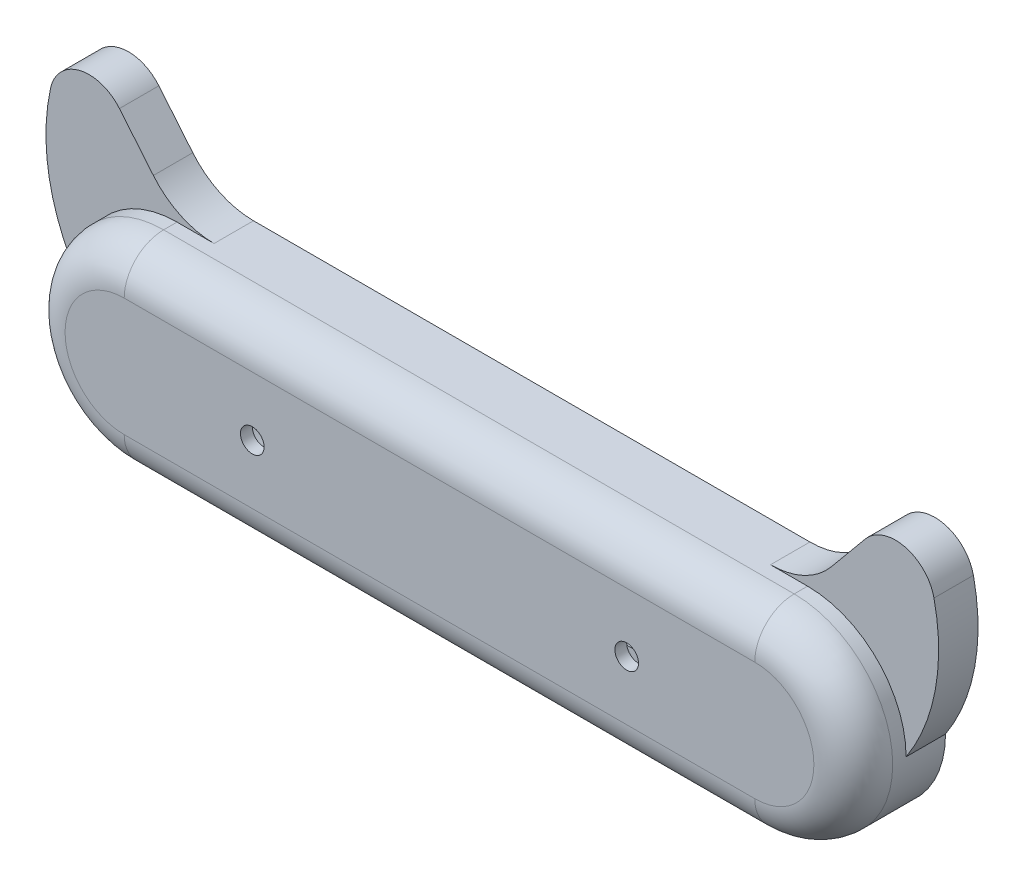
SolidWorks part; units mm, degrees
ref_plane "Front Plane" through (0, 0, 0) normal (0, 0, 1) x (1, 0, 0)
ref_plane "Top Plane" through (0, 0, 0) normal (0, 1, 0) x (1, 0, 0)
ref_plane "Right Plane" through (0, 0, 0) normal (1, 0, 0) x (0, 0, -1)
sketch "Sketch1" plane through (0, 0, 0) normal (0, 0, 1) x (1, 0, 0)
  line L0 (47.5, -14.5) -> (-47.5, -14.5) construction
  line L1 (-47.5, 14.5) -> (47.5, 14.5) construction
  line L2 (80, -25) -> (-80, -25) construction
  line L3 (-80, 25) -> (80, 25) construction
  line L4 (47.5, -14.5) -> (-47.5, -14.5)
  line L5 (-47.5, 14.5) -> (47.5, 14.5)
  line L6 (80, -25) -> (-80, -25)
  line L7 (-80, 25) -> (80, 25)
  arc A0 (47.5, -14.5) -> (47.5, 14.5) centre (47.5, 0) ccw construction
  arc A1 (-47.5, 14.5) -> (-47.5, -14.5) centre (-47.5, 0) ccw construction
  arc A2 (80, -25) -> (80, 25) centre (80, 0) ccw construction
  arc A3 (-80, 25) -> (-80, -25) centre (-80, 0) ccw construction
  arc A4 (47.5, -14.5) -> (47.5, 14.5) centre (47.5, 0) ccw
  arc A5 (-47.5, 14.5) -> (-47.5, -14.5) centre (-47.5, 0) ccw
  arc A6 (80, -25) -> (80, 25) centre (80, 0) ccw
  arc A7 (-80, 25) -> (-80, -25) centre (-80, 0) ccw
  circle A8 centre (75, -15) radius 2 construction
  circle A9 centre (75, 15) radius 2 construction
  circle A10 centre (-75, -15) radius 2 construction
  circle A11 centre (-75, 15) radius 2 construction
  circle A12 centre (75, -15) radius 2
  circle A13 centre (75, 15) radius 2
  circle A14 centre (-75, -15) radius 2
  circle A15 centre (-75, 15) radius 2
extrude "Boss-Extrude1" add sketch "Sketch1" along normal blind 4
sketch "Sketch2" plane through (0, 0, 4) normal (0, 0, 1) x (1, 0, 0)
  line L0 (47.5, 14.5) -> (-47.5, 14.5) construction
  line L1 (47.5, 14.5) -> (-47.5, 14.5)
  line L2 (80, 25) -> (-80, 25)
  line L3 (-80, -25) -> (80, -25)
  line L4 (80, 25) -> (-80, 25)
  line L5 (-80, -25) -> (80, -25)
  line L6 (-47.5, -14.5) -> (47.5, -14.5) construction
  line L7 (-47.5, -14.5) -> (47.5, -14.5)
  arc A0 (-47.5, 14.5) -> (-47.5, -14.5) centre (-47.5, 0) ccw construction
  arc A1 (-47.5, 14.5) -> (-47.5, -14.5) centre (-47.5, 0) ccw
  arc A2 (80, -25) -> (80, 25) centre (80, 0) ccw
  arc A3 (-80, 25) -> (-80, -25) centre (-80, 0) ccw
  arc A4 (80, -25) -> (80, 25) centre (80, 0) ccw
  arc A5 (-80, 25) -> (-80, -25) centre (-80, 0) ccw
  arc A6 (47.5, -14.5) -> (47.5, 14.5) centre (47.5, 0) ccw construction
  arc A7 (47.5, -14.5) -> (47.5, 14.5) centre (47.5, 0) ccw
  dimension "D1" = 0
extrude "Boss-Extrude2" add sketch "Sketch2" along normal up to surface (16.4 mm away)
sketch "Sketch3" plane through (0, 0, 20.4) normal (0, 0, 1) x (1, 0, 0)
  line L2 (80, 25) -> (-80, 25)
  line L3 (-80, -25) -> (80, -25)
  line L4 (80, 25) -> (-80, 25)
  line L5 (-80, -25) -> (80, -25)
  circle A0 centre (-47.5, 0) radius 3
  arc A2 (-80, 25) -> (-80, -25) centre (-80, 0) ccw
  arc A3 (80, -25) -> (80, 25) centre (80, 0) ccw
  arc A4 (-80, 25) -> (-80, -25) centre (-80, 0) ccw
  arc A5 (80, -25) -> (80, 25) centre (80, 0) ccw
  circle A6 centre (47.5, 0) radius 3
  dimension "D2" = 6
  dimension "D3" = 6
  dimension "D1" = 0
extrude "Boss-Extrude3" add sketch "Sketch3" along normal blind 3
fillet "Fillet1" radius 10 4 edges at (105, 0, 23.4) (0, -25, 23.4) (-105, 0, 23.4) (0, 25, 23.4)
sketch "Sketch4" plane through (0, 0, 0) normal (0, 0, -1) x (-1, 0, 0)
  line L0 (0, 0) -> (-47.5, 0) construction
  line L1 (80, 25) -> (105, 55.2066)
  line L5 (0, 0) -> (0, -83.9707) construction
  line L8 (-80, 25) -> (-105, 55.2066)
  arc A1 (-80, 25) -> (-80, -25) centre (-80, 0) ccw construction
  arc A2 (-80, 25) -> (-105, 0) centre (-80, 0) ccw
  arc A5 (-105, 0) -> (-105, 55.2066) centre (-62.9755, 27.6033) cw
  arc A8 (105, 0) -> (105, 55.2066) centre (62.9755, 27.6033) ccw
  arc A9 (80, -25) -> (80, 25) centre (80, 0) ccw construction
  arc A10 (105, 0) -> (80, 25) centre (80, 0) ccw
extrude "Boss-Extrude4" add sketch "Sketch4" against normal blind 10
fillet "Fillet3" radius 10 2 edges at (-105, 55.2066, 5) (105, 55.2066, 5)
sketch "Sketch8" plane through (0, 0, 0) normal (0, 0, -1) x (-1, 0, 0)
  line L12 (-100.8209, 2.745) -> (-83.8519, 21.8121)
  line L13 (-83.8519, 21.8121) -> (-98.4587, 39.461)
  line L14 (-83.8519, 21.8121) -> (-98.4587, 39.461)
  line L15 (0, 0) -> (0, 25) construction
  line L16 (-80, 25) -> (80, 25) construction
  line L17 (83.8519, 21.8121) -> (98.4587, 39.461)
  line L18 (100.8209, 2.745) -> (83.8519, 21.8121)
  arc A15 (98.4587, 39.461) -> (107.1934, 37.3492) centre (102.3106, 36.273) cw
  arc A16 (107.1934, 37.3492) -> (100.8209, 2.745) centre (62.9755, 27.6033) cw
  arc A17 (-107.1934, 37.3492) -> (-100.8209, 2.745) centre (-62.9755, 27.6033) ccw
  arc A18 (-98.4587, 39.461) -> (-107.1934, 37.3492) centre (-102.3106, 36.273) ccw
  arc A19 (-107.1934, 37.3492) -> (-100.8209, 2.745) centre (-62.9755, 27.6033) ccw
  arc A20 (-98.4587, 39.461) -> (-107.1934, 37.3492) centre (-102.3106, 36.273) ccw
  dimension "D1" = 5
extrude "Cut-Extrude3" cut sketch "Sketch8" against normal blind 7.5
sketch "Sketch9" plane through (0, -25, 0) normal (0, -1, 0) x (1, 0, 0)
  line L0 (0, 13.4) -> (40, 13.4) construction
  line L1 (80, 13.4) -> (-80, 13.4) construction
  line L3 (27.5, 6.4) -> (52.5, 6.4)
  line L4 (27.5, 6.4) -> (27.5, 20.4)
  line L5 (27.5, 20.4) -> (52.5, 20.4)
  line L6 (52.5, 6.4) -> (52.5, 20.4)
  line L7 (27.5, 6.4) -> (52.5, 20.4) construction
  line L8 (27.5, 20.4) -> (52.5, 6.4) construction
  dimension "D1" = 25
  dimension "D2" = 14
extrude "Cut-Extrude4" cut sketch "Sketch9" against normal blind 15
fillet "Fillet4" radius 20 2 edges at (-80, 25, 5) (80, 25, 5)
sketch "Sketch10" plane through (0, -25, 0) normal (0, -1, 0) x (1, 0, 0)
  line L0 (0, 0) -> (0, 13.4) construction
  line L1 (-80, 0) -> (80, 0) construction
  line L2 (27.5, 13.4) -> (-80, 13.4) construction
  line L3 (0, 6.7) -> (-5, 6.7) construction
  circle A0 centre (-5, 6.7) radius 2.55
  circle A1 centre (5, 6.7) radius 2.55
  dimension "D2" = 5.1
  dimension "D1" = 5
extrude "Cut-Extrude5" cut sketch "Sketch10" against normal blind 4
